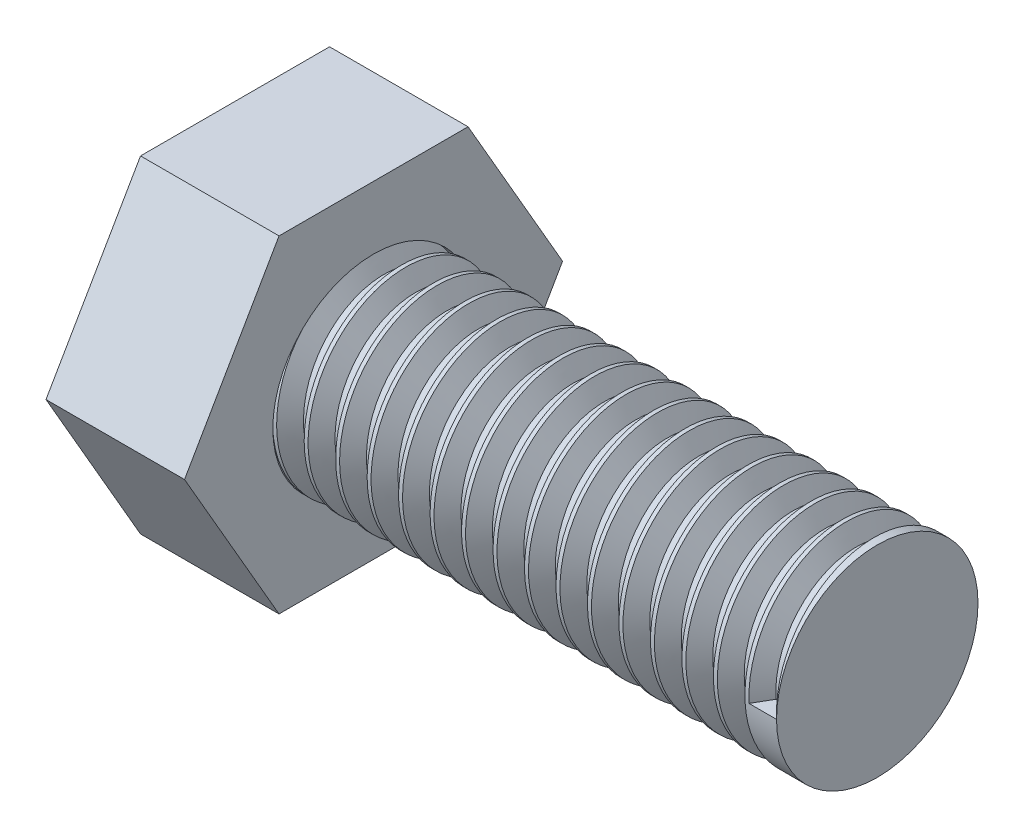
SolidWorks part; units mm, degrees
ref_plane "Front Plane" through (0, 0, 0) normal (0, 0, 1) x (1, 0, 0)
ref_plane "Top Plane" through (0, 0, 0) normal (0, 1, 0) x (1, 0, 0)
ref_plane "Right Plane" through (0, 0, 0) normal (1, 0, 0) x (0, 0, -1)
sketch "Sketch1" plane through (0, 0, 0) normal (0, 0, 1) x (1, 0, 0)
  line L0 (0, 0) -> (20, 0) construction
  line L1 (20, 0) -> (20, 4)
  line L2 (20, 4) -> (0, 4)
  line L6 (0, 0) -> (20, 0)
  line L7 (0, 4) -> (0, 0)
  dimension "D1" = 4
  dimension "D2" = 20
revolve "Revolve1" add sketch "Sketch1" angle 360 about L0
sketch "Sketch2" plane through (0, 0, 0) normal (-1, 0, 0) x (0, 0, 1)
  line L1 (7.5056, 0) -> (3.7528, 6.5)
  line L2 (3.7528, 6.5) -> (-3.7528, 6.5)
  line L3 (-3.7528, 6.5) -> (-7.5056, 0)
  line L4 (-7.5056, 0) -> (-3.7528, -6.5)
  line L5 (-3.7528, -6.5) -> (3.7528, -6.5)
  line L6 (3.7528, -6.5) -> (7.5056, 0)
  circle A0 centre (0, 0) radius 6.5 construction
  point P1 (3.7068, 6.5263)
  dimension "D1" = 13
extrude "Boss-Extrude1" add sketch "Sketch2" along normal blind 5.5
thread "Thread1" pitch 1.25 method cut profile "Thread Profile1" start angle 0, offset 0, length 0, pitch 1.25, diameter 8
ref_plane "Plane1" through (20, 0, 4) normal (0, -1, 0) x (0, 0, 1)
sketch "Thread Profile1" plane through (20, 0, 4) normal (0, -1, 0) x (0, 0, 1)
  line L0 (0, 0) -> (0, 1.25) construction
  line L11 (0, 0) -> (0, 1.0937)
  line L12 (0, 1.0937) -> (-0.6766, 0.7031)
  line L13 (-0.6766, 0.7031) -> (-0.6766, 0.3906)
  line L15 (-0.6766, 0.3906) -> (0, 0)
  line L17 (-0.6766, 0.5469) -> (0, 0.5469) construction
  point P2 (0, 0)
  dimension "Pitch" = 1.25
  dimension "Profile_Angle" = 60
  dimension "Profile_Land" = 0.3125
  dimension "Profile_Height" = 0.6766
